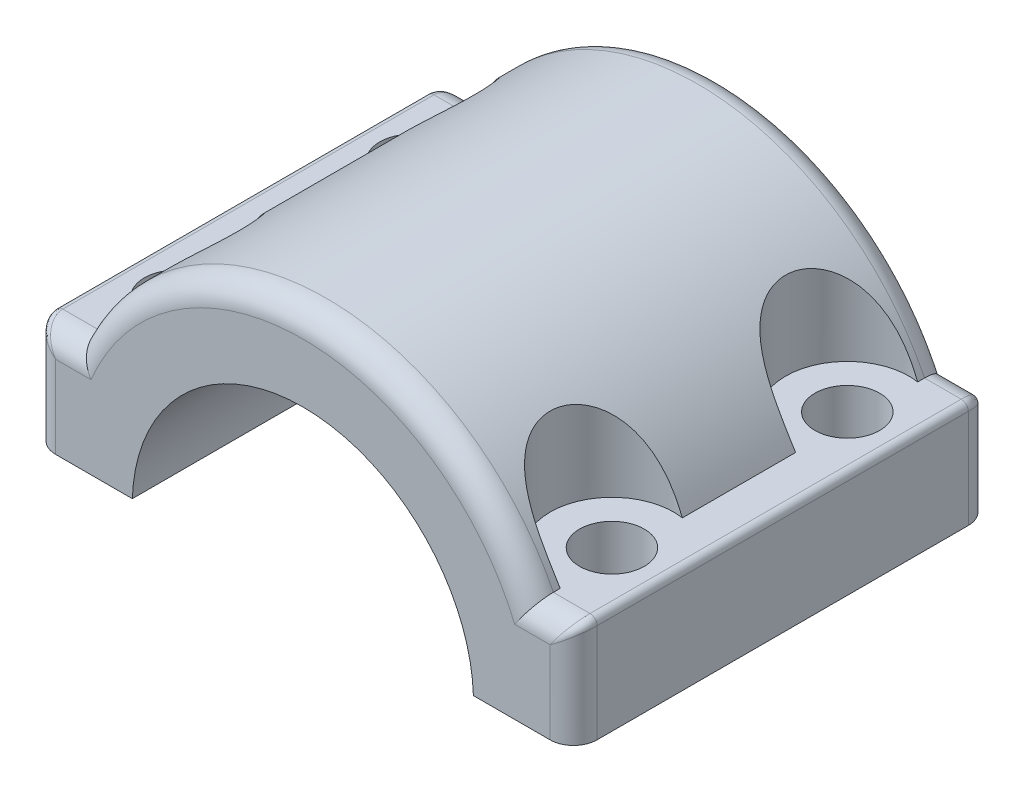
SolidWorks part; units mm, degrees
ref_plane "Front Plane" through (0, 0, 0) normal (0, 0, 1) x (1, 0, 0)
ref_plane "Top Plane" through (0, 0, 0) normal (0, 1, 0) x (1, 0, 0)
ref_plane "Right Plane" through (0, 0, 0) normal (1, 0, 0) x (0, 0, -1)
sketch "Sketch1" plane through (0, 0, 0) normal (0, 1, 0) x (1, 0, 0)
  line L1 (0, 0) -> (46, 0) construction
  line L2 (0, 0) -> (0, -35.5399) construction
  line L3 (0, -35.5399) -> (46, -35.5399) construction
  line L4 (46, 0) -> (46, -35.5399) construction
  line L6 (8.5, -35.5399) -> (2, -35.5399) construction
  dimension "D1" = 46
sketch "Sketch2" plane through (0, 0, 0) normal (0, 0, 1) x (1, 0, 0)
  line L0 (23, 21.5) -> (23, 14.5) construction
  line L1 (46, 0.5) -> (37.4914, 0.5)
  line L2 (46, 0.5) -> (46, 9.5)
  line L3 (46, 9.5) -> (42.2873, 9.5)
  line L4 (0, 0.5) -> (0, 9.5)
  line L5 (3.7127, 9.5) -> (0, 9.5)
  line L6 (8.5086, 0.5) -> (0, 0.5)
  line L7 (0, 0) -> (46, 0) construction
  line L8 (0, 0) -> (46, 0) construction
  arc A0 (37.4914, 0.5) -> (8.5086, 0.5) centre (23, 0) ccw
  arc A1 (3.7127, 9.5) -> (42.2873, 9.5) centre (23, 0) cw
  circle A3 centre (23, 0) radius 14.5 construction
  dimension "D3" = 7
  dimension "D4" = 29
  dimension "D1" = 0.5
  dimension "D2" = 9
extrude "Boss-Extrude1" add sketch "Sketch2" along normal up to vertex (35.5399 mm away) up to point (46, 0, 35.5399)
ref_plane "Plane1" through (0, 9.5, 0) normal (0, 1, 0) x (1, 0, 0)
sketch "Sketch3" plane through (0, 9.5, 0) normal (0, 1, 0) x (1, 0, 0)
  line L0 (41.4914, -27.77) -> (4.5086, -27.77) construction
  line L2 (41.4914, -27.77) -> (46, -27.77) construction
  line L3 (46, -35.5399) -> (46, 0) construction
  line L4 (4.5086, -27.77) -> (0, -27.77) construction
  line L5 (0, -35.5399) -> (0, 0) construction
  line L6 (8.5086, -35.5399) -> (8.5086, 0) construction
  line L7 (41.4914, -27.77) -> (41.4914, -35.5399) construction
  line L8 (0, -35.5399) -> (46, -35.5399) construction
  line L9 (41.4914, -7.77) -> (41.4914, 0) construction
  line L10 (0, 0) -> (46, 0) construction
  circle A0 centre (41.4914, -27.77) radius 2.75
  circle A1 centre (4.5086, -27.77) radius 2.75
  circle A2 centre (4.5086, -7.77) radius 2.75
  circle A3 centre (41.4914, -7.77) radius 2.75
  point P12 (23, -27.77)
  dimension "D1" = 5.5
  dimension "D2" = 20
  dimension "D3" = 4
extrude "Cut-Extrude1" cut sketch "Sketch3" against normal up to surface (9 mm away) and the other way through all up to face at (41.7457, 0.5, 17.77)
sketch "Sketch4" plane through (0, 9.5, 0) normal (0, 1, 0) x (1, 0, 0)
  circle A0 centre (41.4914, -27.77) radius 5.25
  circle A1 centre (4.5, -27.77) radius 5.25
  circle A2 centre (4.5, -7.77) radius 5.25
  circle A3 centre (41.4914, -7.77) radius 5.25
  circle A6 centre (4.5, -27.77) radius 2.1 construction
  circle A7 centre (4.5, -7.77) radius 2.1 construction
  arc A8 (42.2873, -30.4023) -> (42.2873, -25.1377) centre (41.4914, -27.77) ccw construction
  arc A9 (42.2873, -10.4023) -> (42.2873, -5.1377) centre (41.4914, -7.77) ccw construction
  dimension "D1" = 10.5
extrude "Cut-Extrude2" cut sketch "Sketch4" along normal through all
fillet "Fillet1" radius 2 10 edges at (1.8563, 9.5, 35.5399) (0, 5, 35.5399) (0, 5, 0) (1.8563, 9.5, 0) (23, 21.5, 0) (46, 5, 0) (44.1437, 9.5, 0) (23, 21.5, 35.5399) (44.1437, 9.5, 35.5399) (46, 5, 35.5399)
fillet "Fillet2" radius 0.6 6 edges at (45.4142, 8.9142, 34.9541) (45.4142, 8.9142, 0.5858) (0.5858, 8.9142, 34.9541) (0.5858, 8.9142, 0.5858) (46, 9.5, 17.77) (0, 9.5, 17.77)
